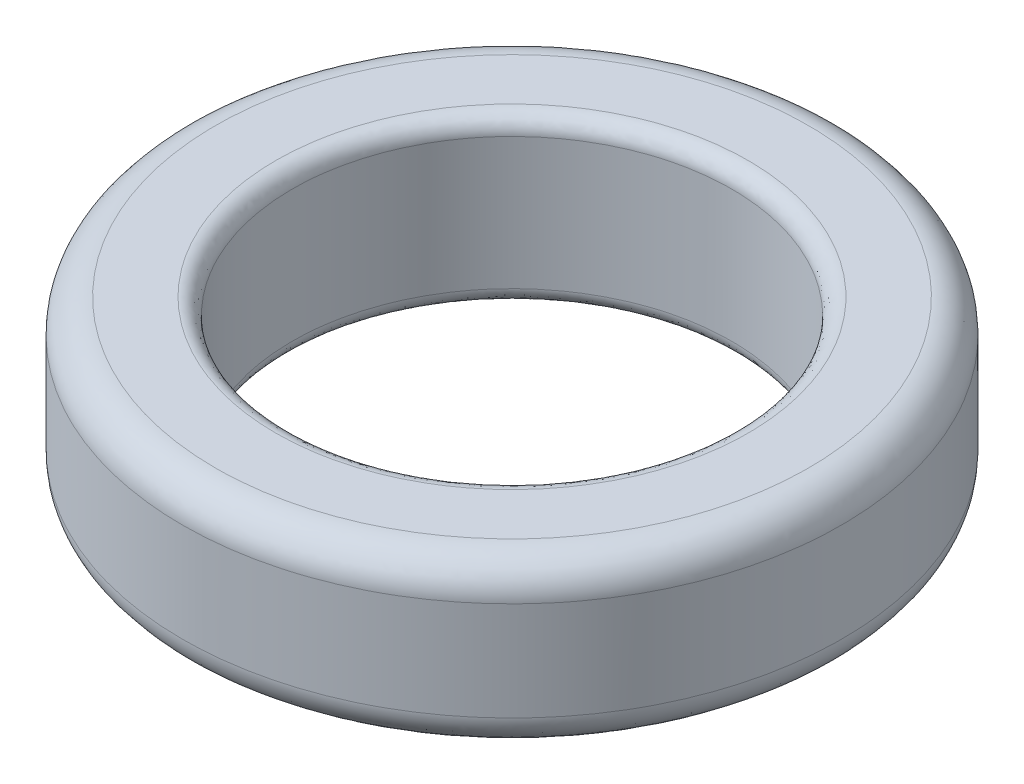
SolidWorks part; units mm, degrees
ref_plane "Front Plane" through (0, 0, 0) normal (0, 0, 1) x (1, 0, 0)
ref_plane "Top Plane" through (0, 0, 0) normal (0, 1, 0) x (1, 0, 0)
ref_plane "Right Plane" through (0, 0, 0) normal (1, 0, 0) x (0, 0, -1)
other "Configuration Table"
sketch "Sketch1" plane through (0, 0, 0) normal (0, 1, 0) x (1, 0, 0)
  circle A0 centre (0, 0) radius 30
  circle A1 centre (0, 0) radius 20
  dimension "D1" = 60
  dimension "D2" = 40
extrude "Boss-Extrude1" add sketch "Sketch1" along normal blind 15
fillet "Fillet1" radius 3 2 edges at (0, 0, 30) (0, 15, 30) first distance on face at (0, 15, 30)
fillet "Fillet2" radius 1.5 2 edges at (0, 0, 20) (0, 15, 20)
